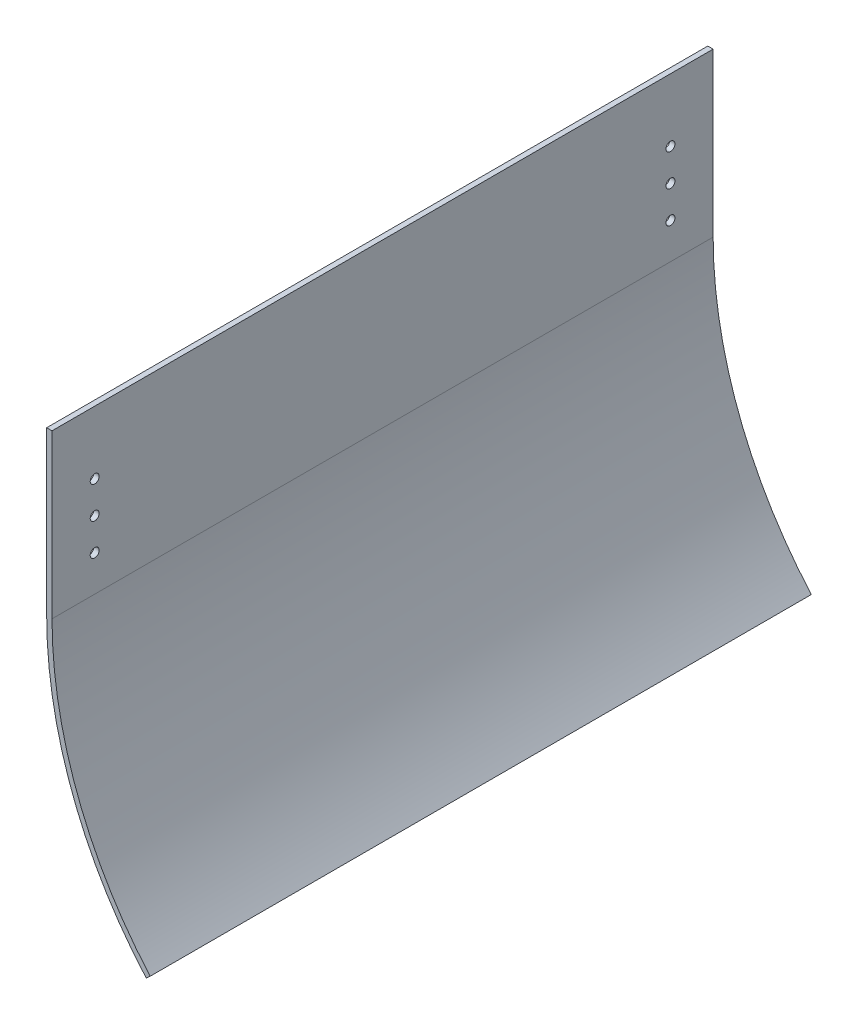
SolidWorks part; units mm, degrees
ref_plane "Front Plane" through (0, 0, 0) normal (0, 0, 1) x (1, 0, 0)
ref_plane "Top Plane" through (0, 0, 0) normal (0, 1, 0) x (1, 0, 0)
ref_plane "Right Plane" through (0, 0, 0) normal (1, 0, 0) x (0, 0, -1)
sketch "Sketch1" plane through (0, 0, 0) normal (0, 0, 1) x (1, 0, 0)
  line L2 (812.5417, 1387.3698) -> (812.5417, 1484.2708)
  line L4 (815.7167, 1387.3698) -> (815.7167, 1484.2708)
  line L5 (812.5417, 1484.2708) -> (815.7167, 1484.2708)
  line L6 (874.1429, 1232.3666) -> (871.7578, 1230.2708)
  arc A0 (812.5417, 1387.3698) -> (871.7578, 1230.2708) centre (1050.5397, 1387.3698) ccw
  arc A1 (815.7167, 1387.3698) -> (874.1429, 1232.3666) centre (1050.5397, 1387.3698) ccw
  dimension "D1" = 237.998
  dimension "D3" = 237.998
  dimension "D4" = 3.175
extrude "Boss-Extrude1" add sketch "Sketch1" along normal blind 393.446
sketch "Sketch2" plane through (815.7167, 0, 0) normal (1, 0, 0) x (0, 0, -1)
  line L0 (-393.446, 1484.2708) -> (0, 1484.2708) construction
  line L1 (-393.446, 1387.3698) -> (-393.446, 1484.2708) construction
  line L2 (-196.723, 1484.2708) -> (-196.723, 1387.3698) construction
  line L3 (-393.446, 1387.3698) -> (0, 1387.3698) construction
  circle A0 centre (-368.046, 1446.8058) radius 2.667
  circle A1 centre (-368.046, 1427.7558) radius 2.667
  circle A2 centre (-368.046, 1408.7058) radius 2.667
  circle A3 centre (-25.4, 1408.7058) radius 2.667
  circle A4 centre (-25.4, 1427.7558) radius 2.667
  circle A5 centre (-25.4, 1446.8058) radius 2.667
  dimension "D1" = 5.334
  dimension "D2" = 5.334
  dimension "D3" = 5.334
  dimension "D4" = 37.465
  dimension "D5" = 19.05
  dimension "D6" = 19.05
  dimension "D7" = 25.4
  dimension "D8" = 25.4
  dimension "D9" = 25.4
extrude "Cut-Extrude1" cut sketch "Sketch2" against normal through all
